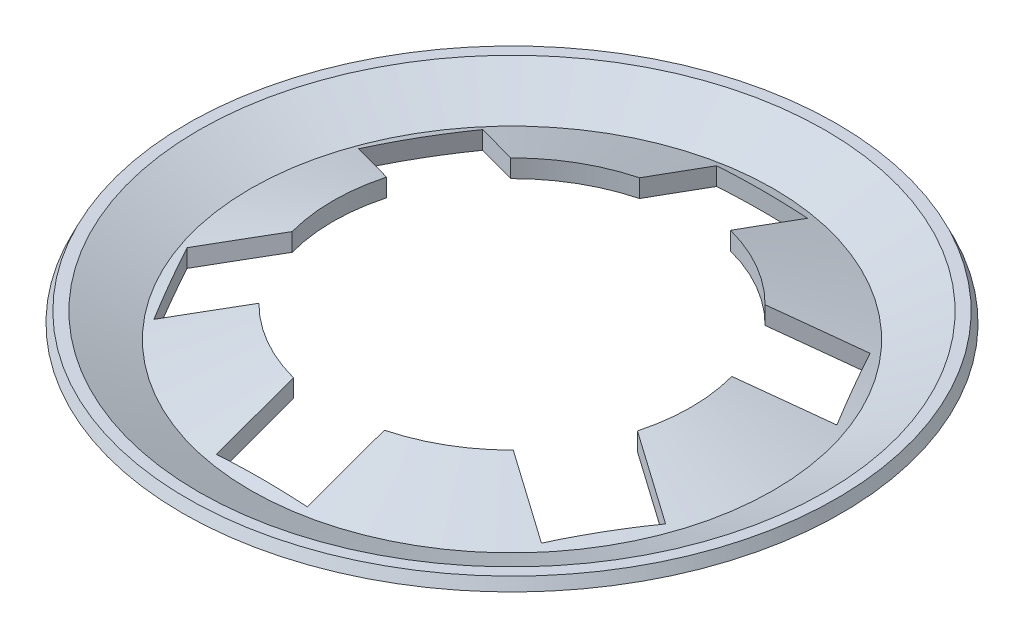
SolidWorks part; units mm, degrees
material "1060 Сплав"
ref_plane "Front Plane" through (0, 0, 0) normal (0, 0, 1) x (1, 0, 0)
ref_plane "Top Plane" through (0, 0, 0) normal (0, 1, 0) x (1, 0, 0)
ref_plane "Right Plane" through (0, 0, 0) normal (1, 0, 0) x (0, 0, -1)
sketch "Sketch2" plane through (0, 0, 0) normal (0, 0, 1) x (1, 0, 0)
  line L0 (-4, 1.0883) -> (-5.842, 0.4014)
  line L1 (-5.842, 0.4014) -> (-7.0032, 0.9516)
  line L2 (-7.0032, 0.9516) -> (-7.2572, 0.9516)
  line L3 (-7.2572, 0.9516) -> (-7.366, 0.722)
  line L4 (-7.366, 0.722) -> (-5.842, 0)
  line L5 (-5.842, 0) -> (-4, 0.6869)
  line L6 (-4, 0.6869) -> (-4, 1.0883)
  line L7 (0, 0) -> (0, 5.5064) construction
  line L8 (0, 0) -> (-4.0763, 0) construction
  dimension "D1" = 0.3761
  dimension "D2" = 14.732
  dimension "D3" = 0.3627
  dimension "D4" = 25.35
  dimension "D5" = 25.35
  dimension "D6" = 0.1087
  dimension "D7" = 11.684
  dimension "D8" = 8
  dimension "D10" = 20.45
revolve "Revolve1" add sketch "Sketch2" angle 360 about L7
ref_axis "Axis2" through (0, 1.0883, 0) along (0, -1, 0)
sketch "Sketch3" plane through (0, 0, 0) normal (0, 1, 0) x (1, 0, 0)
  line L0 (1.016, 5.588) -> (1.016, 0)
  line L1 (-1.016, 5.588) -> (1.016, 5.588)
  line L2 (-1.016, 0) -> (-1.016, 5.588)
  line L3 (0, 0) -> (0, 7.9655) construction
  line L4 (-1.016, 0) -> (1.016, 0)
  dimension "D1" = 5.588
  dimension "D2" = 2.032
extrude "Extrude1" cut sketch "Sketch3" along normal through all
pattern_circular "CirPattern1" count 6 over 360 about axis through (0, 1.0883, 0) along (0, -1, 0) of "Extrude1"
